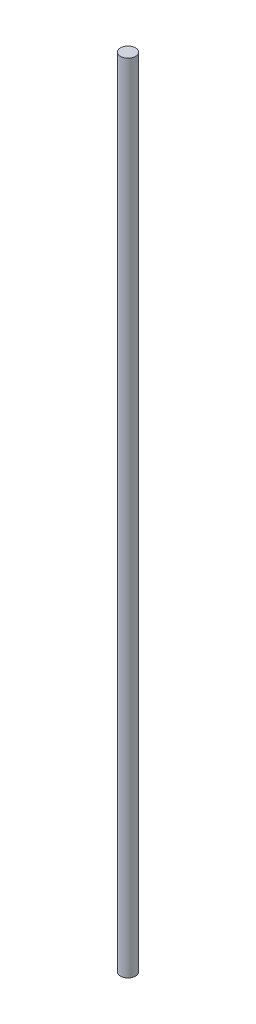
SolidWorks part; units mm, degrees
material "Stainless Steel (ferritic)"
ref_plane "Front Plane" through (0, 0, 0) normal (0, 0, 1) x (1, 0, 0)
ref_plane "Top Plane" through (0, 0, 0) normal (0, 1, 0) x (1, 0, 0)
ref_plane "Right Plane" through (0, 0, 0) normal (1, 0, 0) x (0, 0, -1)
sketch "Sketch1" plane through (0, 0, 0) normal (0, 1, 0) x (1, 0, 0)
  circle A0 centre (0, 0) radius 3
  dimension "D1" = 6
extrude "Boss-Extrude1" add sketch "Sketch1" along normal blind 320
